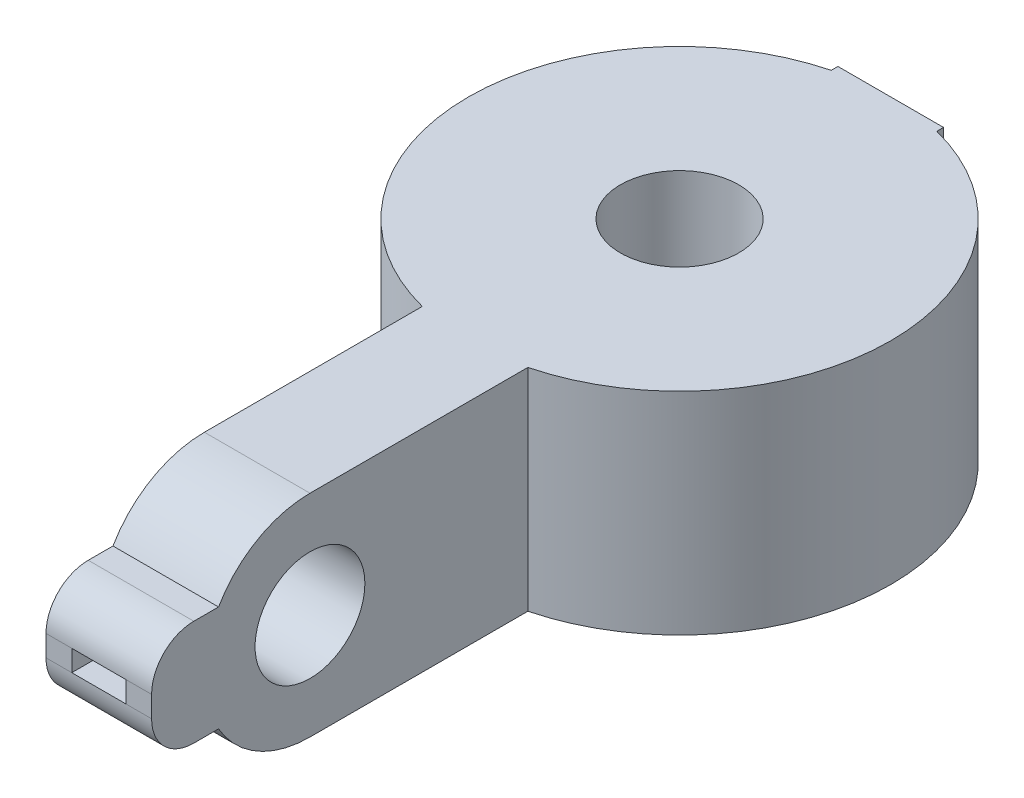
SolidWorks part; units mm, degrees
material "ABS"
ref_plane "Front" through (0, 0, 0) normal (0, 0, 1) x (1, 0, 0)
ref_plane "Top" through (0, 0, 0) normal (0, 1, 0) x (1, 0, 0)
ref_plane "Right" through (0, 0, 0) normal (1, 0, 0) x (0, 0, -1)
sketch "Sketch1" plane through (0, 0, 0) normal (1, 0, 0) x (0, 0, -1)
  line L0 (-3.302, 0) -> (-6.35, 0) construction
  line L1 (0, -6.35) -> (38.1, -6.35)
  line L3 (0, 6.35) -> (38.1, 6.35)
  line L4 (38.1, -6.35) -> (38.1, 6.35)
  line L6 (-9.525, -3.175) -> (-5.4993, -3.175)
  line L7 (-9.525, -3.175) -> (-9.525, 3.175)
  line L8 (-9.525, 3.175) -> (-5.4993, 3.175)
  line L10 (-9.525, -3.175) -> (-9.525, 5.6275) construction
  line L11 (-9.525, 3.175) -> (-9.525, -5.6275) construction
  circle A0 centre (0, 0) radius 3.302
  arc A1 (0, 6.35) -> (-5.4993, 3.175) centre (0, 0) ccw
  arc A2 (-5.4993, -3.175) -> (0, -6.35) centre (0, 0) ccw
  point P8 (-9.525, 0)
  dimension "D1" = 6.604
  dimension "D2" = 12.7
  dimension "D3" = 38.1
  dimension "D4" = 6.35
  dimension "D5" = 9.525
extrude "Boss-Extrude1" add sketch "Sketch1" along normal mid plane 6.35
sketch "Sketch2" plane through (0, 6.35, 0) normal (0, 1, 0) x (1, 0, 0)
  line L0 (3.175, 38.1) -> (-3.175, 38.1) construction
  circle A0 centre (0, 25.4) radius 12.7
  dimension "D1" = 25.4
extrude "Boss-Extrude2" add sketch "Sketch2" against normal up to surface (12.7 mm away) up to face at (0, -6.35, -19.05)
sketch "Sketch3" plane through (0, -6.35, 0) normal (0, -1, 0) x (1, 0, 0)
  circle A0 centre (0, -25.4) radius 3.556
  arc A1 (-3.175, -13.1033) -> (-3.175, -37.6967) centre (0, -25.4) ccw construction
  dimension "D1" = 7.112
extrude "Cut-Extrude1" cut sketch "Sketch3" against normal up to next
sketch "Sketch4" plane through (0, -6.35, 0) normal (0, -1, 0) x (1, 0, 0)
  circle A0 centre (0, -25.4) radius 9.9219
  arc A1 (3.175, -37.6967) -> (3.175, -13.1033) centre (0, -25.4) ccw construction
  dimension "D1" = 19.8438
extrude "Cut-Extrude2" cut sketch "Sketch4" against normal blind 6.35
sketch "Sketch5" plane through (0, 0, -38.1) normal (0, 0, -1) x (-1, 0, 0)
  line L1 (-0.635, -0.0254) -> (0.635, -0.0254)
  line L2 (-0.635, -0.0254) -> (-0.635, 3.175)
  line L3 (-0.635, 3.175) -> (0.635, 3.175)
  line L4 (0.635, -0.0254) -> (0.635, 3.175)
  line L5 (-0.635, -0.0254) -> (0.635, 3.175) construction
  line L6 (-0.635, 3.175) -> (0.635, -0.0254) construction
  line L7 (-3.175, 6.35) -> (3.175, 6.35) construction
  line L8 (-3.175, -6.35) -> (3.175, -6.35) construction
  line L9 (-3.175, -6.35) -> (-3.175, 6.35) construction
  point P0 (0, 0)
  point P8 (0, -6.35)
  dimension "D1" = 1.27
  dimension "D2" = 3.2004
  dimension "D3" = 3.175
  dimension "D4" = 2.54
extrude "Cut-Extrude3" cut sketch "Sketch5" against normal up to surface (2.7985 mm away) up to face at (0, 0, -35.3219)
sketch "Sketch6" plane through (0, 0, 9.525) normal (0, 0, 1) x (1, 0, 0)
  line L1 (-1.6256, 0.635) -> (1.6256, 0.635)
  line L2 (-1.6256, 0.635) -> (-1.6256, -0.635)
  line L3 (-1.6256, -0.635) -> (1.6256, -0.635)
  line L4 (1.6256, 0.635) -> (1.6256, -0.635)
  line L5 (-1.6256, 0.635) -> (1.6256, -0.635) construction
  line L6 (-1.6256, -0.635) -> (1.6256, 0.635) construction
  point P0 (0, 0)
  dimension "D1" = 3.2512
  dimension "D2" = 1.27
extrude "Cut-Extrude4" cut sketch "Sketch6" against normal blind 3.175
fillet "Fillet2" radius 2.54 2 edges at (0, -3.175, 9.525) (0, 3.175, 9.525)
